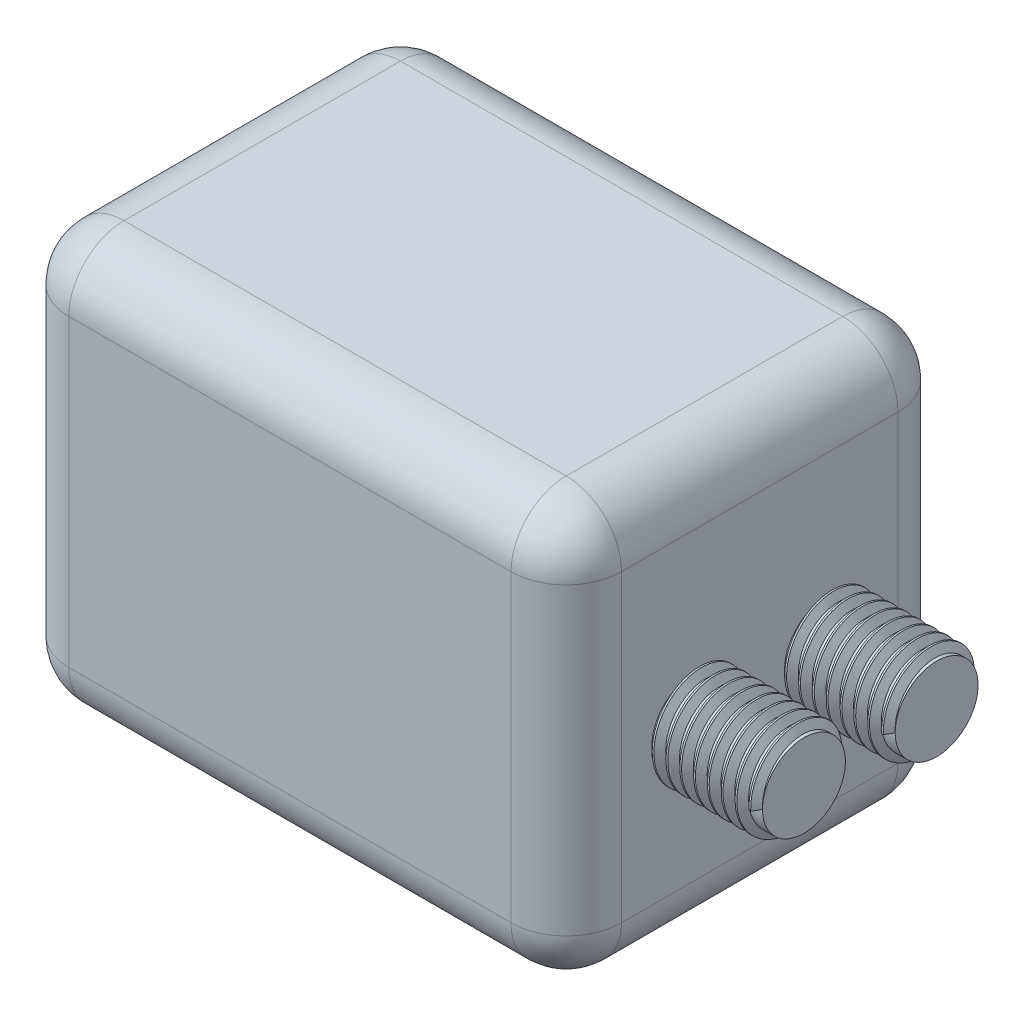
SolidWorks part; units mm, degrees
material "PET"
ref_plane "Front Plane" through (0, 0, 0) normal (0, 0, 1) x (1, 0, 0)
ref_plane "Top Plane" through (0, 0, 0) normal (0, 1, 0) x (1, 0, 0)
ref_plane "Right Plane" through (0, 0, 0) normal (1, 0, 0) x (0, 0, -1)
sketch "Sketch1" plane through (0, 0, 0) normal (0, 0, 1) x (1, 0, 0)
  line L1 (0, 0) -> (100, 0)
  line L2 (0, 0) -> (0, 75)
  line L3 (0, 75) -> (100, 75)
  line L4 (100, 0) -> (100, 75)
  dimension "D1" = 100
  dimension "D2" = 75
extrude "Boss-Extrude1" add sketch "Sketch1" along normal blind 70
fillet "Fillet1" radius 10 12 edges at (50, 75, 70) (100, 37.5, 70) (50, 0, 70) (0, 37.5, 70) (0, 0, 35) (50, 0, 0) (100, 0, 35) (100, 37.5, 0) (100, 75, 35) (0, 75, 35) (0, 37.5, 0) (50, 75, 0)
sketch "Sketch2" plane through (100, 0, 0) normal (1, 0, 0) x (0, 0, -1)
  line L0 (-60, 65) -> (-60, 10) construction
  line L1 (-10, 10) -> (-10, 65) construction
  line L2 (-60, 10) -> (-10, 10) construction
  circle A0 centre (-47, 35) radius 7.5
  circle A1 centre (-23, 35) radius 7.5
  dimension "D1" = 15
  dimension "D2" = 15
  dimension "D3" = 13
  dimension "D4" = 13
  dimension "D5" = 25
  dimension "D6" = 25
extrude "Boss-Extrude2" add sketch "Sketch2" along normal blind 20
thread "Thread1" pitch 2.5 method extrude profile "Thread Profile1" start angle 0, offset 0, length 0, pitch 2.5, diameter 15
ref_plane "Plane1" through (120, 35, 54.5) normal (0, -1, 0) x (0, 0, 1)
sketch "Thread Profile1" plane through (120, 35, 54.5) normal (0, -1, 0) x (0, 0, 1)
  line L0 (0, 0) -> (0, 2.5) construction
  line L1 (0, 0) -> (1.3532, 0.7812)
  line L2 (1.3532, 0.7812) -> (1.3532, 1.0937)
  line L3 (1.3532, 1.0937) -> (0, 1.875)
  line L4 (1.3532, 0.9375) -> (0, 0.9375) construction
  line L11 (0, 0) -> (0, 1.875)
  point P2 (0, 0)
  dimension "Pitch" = 2.5
  dimension "Profile_Angle" = 60
  dimension "Profile_Land" = 0.3125
  dimension "Profile_Height" = 1.3532
thread "Thread2" pitch 2.5 method extrude profile "Thread Profile2" start angle 0, offset 0, length 0, pitch 2.5, diameter 15
ref_plane "Plane2" through (120, 35, 30.5) normal (0, -1, 0) x (0, 0, 1)
sketch "Thread Profile2" plane through (120, 35, 30.5) normal (0, -1, 0) x (0, 0, 1)
  line L0 (0, 0) -> (0, 2.5) construction
  line L1 (0, 0) -> (1.3532, 0.7812)
  line L2 (1.3532, 0.7812) -> (1.3532, 1.0937)
  line L3 (1.3532, 1.0937) -> (0, 1.875)
  line L4 (1.3532, 0.9375) -> (0, 0.9375) construction
  line L11 (0, 0) -> (0, 1.875)
  point P2 (0, 0)
  dimension "Pitch" = 2.5
  dimension "Profile_Angle" = 60
  dimension "Profile_Land" = 0.3125
  dimension "Profile_Height" = 1.3532
sketch "Sketch8" plane through (0, 0, 0) normal (-1, 0, 0) x (0, 0, 1)
  circle A0 centre (33.5575, 23.2357) radius 5
  dimension "D1" = 10
extrude "Cut-Extrude1" cut sketch "Sketch8" against normal blind 10
thread "Thread3" pitch 1.5 method cut profile "Thread Profile3" start angle 0, offset 0, length 8, pitch 1.5, diameter 10
ref_plane "Plane3" through (0, 23.2357, 28.5575) normal (0, -1, 0) x (0, 0, -1)
sketch "Thread Profile3" plane through (0, 23.2357, 28.5575) normal (0, -1, 0) x (0, 0, -1)
  line L0 (0, 0) -> (0, 1.5) construction
  line L1 (0, 0) -> (0.8119, 0.4687)
  line L2 (0.8119, 0.4687) -> (0.8119, 0.6562)
  line L3 (0.8119, 0.6562) -> (0, 1.125)
  line L4 (0.8119, 0.5625) -> (0, 0.5625) construction
  line L11 (0, 0) -> (0, 1.125)
  point P2 (0, 0)
  dimension "Pitch" = 1.5
  dimension "Profile_Angle" = 60
  dimension "Profile_Land" = 0.1875
  dimension "Profile_Height" = 0.8119
